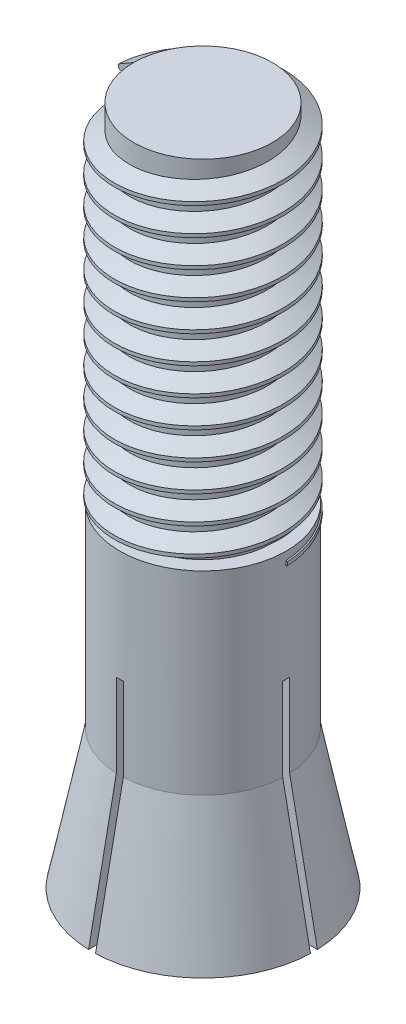
SolidWorks part; units mm, degrees
ref_plane "Front Plane" through (0, 0, 0) normal (0, 0, 1) x (1, 0, 0)
ref_plane "Top Plane" through (0, 0, 0) normal (0, 1, 0) x (1, 0, 0)
ref_plane "Right Plane" through (0, 0, 0) normal (1, 0, 0) x (0, 0, -1)
sketch "Sketch1" plane through (0, 0, 0) normal (0, 1, 0) x (1, 0, 0)
  circle A0 centre (0, 0) radius 4
  dimension "D1" = 8
ref_plane "Plane1" through (0, 5, 0) normal (0, 1, 0) x (1, 0, 0)
sketch "Sketch2" plane through (0, 5, 0) normal (0, 1, 0) x (1, 0, 0)
  circle A0 centre (0, 0) radius 3
  dimension "D1" = 6
loft "Loft1" add profiles "Sketch1", "Sketch2" connector at (-2.8177, 0, 2.8391) connector at (-2.1151, 5, 2.1275)
sketch "Sketch3" plane through (0, 5, 0) normal (0, 1, 0) x (1, 0, 0)
  circle A0 centre (0, 0) radius 3
  circle A2 centre (0, 0) radius 3 construction
extrude "Boss-Extrude1" add sketch "Sketch3" along normal blind 7
sketch "Sketch4" plane through (0, 12, 0) normal (0, 1, 0) x (1, 0, 0)
  circle A0 centre (0, 0) radius 2.5
  circle A1 centre (0, 0) radius 3 construction
  dimension "D1" = 0.5
extrude "Boss-Extrude2" add sketch "Sketch4" along normal blind 12.5
sketch "Sketch5" plane through (0, 0, 0) normal (1, 0, 0) x (0, 0, -1)
  line L1 (-0.125, -8) -> (0.125, -8)
  line L2 (-0.125, -8) -> (-0.125, 8)
  line L3 (-0.125, 8) -> (0.125, 8)
  line L4 (0.125, -8) -> (0.125, 8)
  line L5 (-0.125, -8) -> (0.125, 8) construction
  line L6 (-0.125, 8) -> (0.125, -8) construction
  point P0 (0, 0)
  dimension "D1" = 16
  dimension "D2" = 0.25
extrude "Cut-Extrude1" cut sketch "Sketch5" against normal blind 12.5
pattern_circular "CirPattern1" count 4 every 90 about axis through (0, 24.5, 0) along (0, -1, 0) of "Cut-Extrude1" reverse direction yes
thread "Thread1" pitch 1 method extrude profile "Thread Profile1" start angle 0, offset 0, length 0, pitch 1, diameter 5
ref_plane "Plane2" through (-2.5, 24.5, 0) normal (0, 0, 1) x (-1, 0, 0)
sketch "Thread Profile1" plane through (-2.5, 24.5, 0) normal (0, 0, 1) x (-1, 0, 0)
  line L0 (0, 0) -> (0, 1) construction
  line L1 (0, 0) -> (0.5413, 0.3125)
  line L2 (0.5413, 0.3125) -> (0.5413, 0.4375)
  line L3 (0.5413, 0.4375) -> (0, 0.75)
  line L4 (0.5413, 0.375) -> (0, 0.375) construction
  line L11 (0, 0) -> (0, 0.75)
  point P2 (0, 0)
  dimension "Pitch" = 1
  dimension "Profile_Angle" = 60
  dimension "Profile_Land" = 0.125
  dimension "Profile_Height" = 0.5413
sketch "Sketch9" plane through (0, 0, 0) normal (0, -1, 0) x (1, 0, 0)
  circle A0 centre (0, 0) radius 1.55
  dimension "D1" = 3.1
extrude "Cut-Extrude2" cut sketch "Sketch9" against normal blind 14.5
